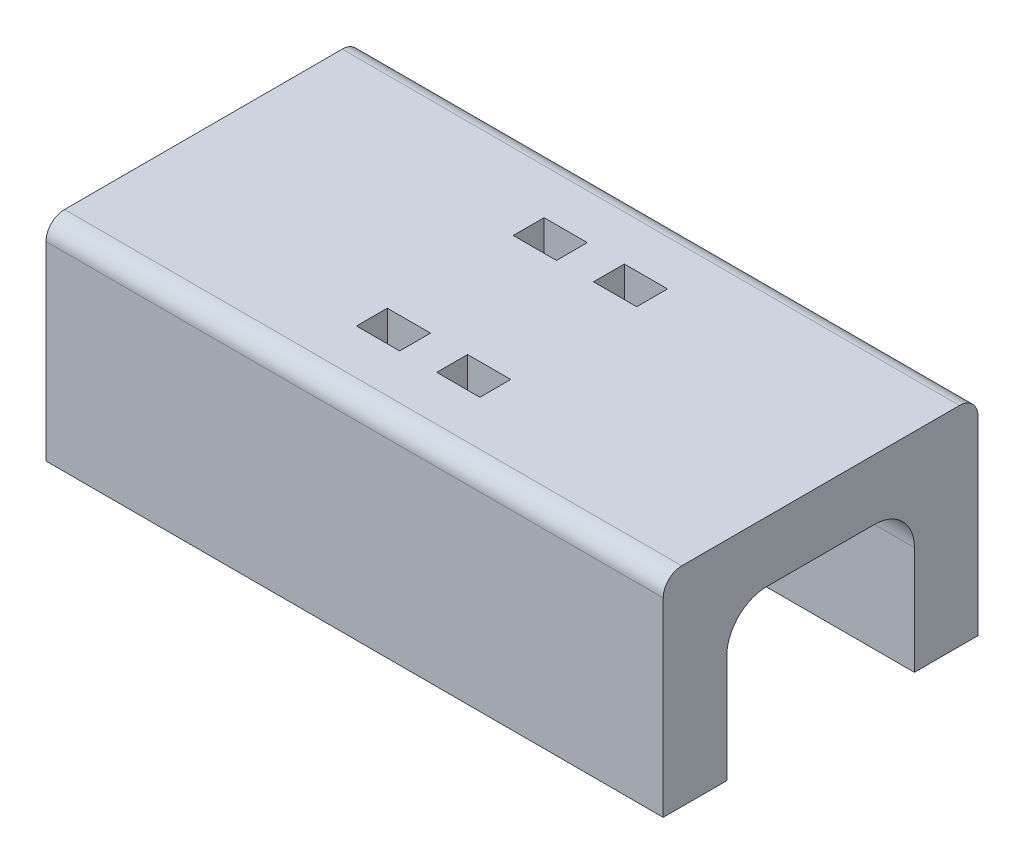
SolidWorks part; units mm, degrees
ref_plane "Front Plane" through (0, 0, 0) normal (0, 0, 1) x (1, 0, 0)
ref_plane "Top Plane" through (0, 0, 0) normal (0, 1, 0) x (1, 0, 0)
ref_plane "Right Plane" through (0, 0, 0) normal (1, 0, 0) x (0, 0, -1)
sketch "Sketch1" plane through (0, 0, 0) normal (0, 1, 0) x (1, 0, 0)
  line L1 (0, 0) -> (50, 0)
  line L2 (0, 0) -> (0, 25.5)
  line L3 (0, 25.5) -> (50, 25.5)
  line L4 (50, 0) -> (50, 25.5)
  dimension "D1" = 50
  dimension "D2" = 25.5
extrude "Boss-Extrude1" add sketch "Sketch1" along normal blind 16.9
sketch "Sketch3" plane through (0, 0, 0) normal (0, -1, 0) x (1, 0, 0)
  line L0 (50, 0) -> (50, -25.5) construction
  line L1 (0, -20.35) -> (50, -20.35)
  line L2 (0, -20.35) -> (0, -5.15)
  line L3 (0, -5.15) -> (50, -5.15)
  line L4 (50, -20.35) -> (50, -5.15)
  line L5 (0, -20.35) -> (50, -5.15) construction
  line L6 (0, -5.15) -> (50, -20.35) construction
  line L7 (0, 0) -> (50, 0) construction
  point P0 (25, -12.75)
  point P7 (25, 0)
  dimension "D1" = 50
  dimension "D2" = 15.2
  dimension "D3" = 12.75
extrude "Cut-Extrude1" cut sketch "Sketch3" against normal blind 12
sketch "Sketch4" plane through (0, 12, 0) normal (0, -1, 0) x (1, 0, 0)
  line L6 (50, -5.15) -> (0, -5.15) construction
  line L7 (20, -20.5) -> (30, -20.5)
  line L8 (20, -20.5) -> (20, -5.15)
  line L9 (20, -5.15) -> (30, -5.15)
  line L10 (30, -20.5) -> (30, -5.15)
  point P12 (25, -12.75)
  dimension "D1" = 10
extrude "Boss-Extrude2" add sketch "Sketch4" along normal blind 12
sketch "Sketch5" plane through (0, 0, 0) normal (0, -1, 0) x (1, 0, 0)
  line L1 (20, -5.15) -> (23.5, -5.15)
  line L2 (20, -5.15) -> (20, -7.65)
  line L3 (20, -7.65) -> (23.5, -7.65)
  line L4 (23.5, -5.15) -> (23.5, -7.65)
  line L5 (30, -5.15) -> (26.5, -5.15)
  line L6 (30, -5.15) -> (30, -7.65)
  line L7 (30, -7.65) -> (26.5, -7.65)
  line L8 (26.5, -5.15) -> (26.5, -7.65)
  line L9 (30, -20.35) -> (26.5, -20.35)
  line L10 (30, -20.35) -> (30, -17.85)
  line L11 (30, -17.85) -> (26.5, -17.85)
  line L12 (26.5, -20.35) -> (26.5, -17.85)
  line L13 (20, -20.35) -> (23.5, -20.35)
  line L14 (20, -20.35) -> (20, -17.85)
  line L15 (20, -17.85) -> (23.5, -17.85)
  line L16 (23.5, -20.35) -> (23.5, -17.85)
  dimension "D1" = 3.5
  dimension "D2" = 2.5
  dimension "D3" = 2.5
  dimension "D4" = 3.5
  dimension "D5" = 3.5
  dimension "D6" = 2.5
  dimension "D7" = 2.5
  dimension "D8" = 3.5
extrude "Cut-Extrude2" cut sketch "Sketch5" against normal through all
sketch "Sketch6" plane through (30, 0, 0) normal (1, 0, 0) x (0, 0, -1)
  circle A0 centre (12.75, 6) radius 2.5
  dimension "D1" = 5
extrude "Cut-Extrude3" cut sketch "Sketch6" against normal blind 2
sketch "Sketch7" plane through (20, 0, 0) normal (-1, 0, 0) x (0, 0, 1)
  circle A0 centre (-12.75, 6) radius 2.5
  dimension "D1" = 5
extrude "Cut-Extrude4" cut sketch "Sketch7" against normal blind 2
sketch "Sketch8" plane through (0, 0, 0) normal (0, -1, 0) x (1, 0, 0)
  line L0 (0, -2.575) -> (50, -2.575) construction
  line L10 (0, -5.15) -> (0, 0) construction
  line L12 (50, 0) -> (50, -5.15) construction
  line L13 (0, -22.925) -> (50, -22.925) construction
  line L14 (0, -25.5) -> (0, -20.35) construction
  line L15 (50, -20.35) -> (50, -25.5) construction
  line L16 (30, -17.85) -> (30, -7.65) construction
  line L17 (0, 0) -> (50, 0) construction
  circle A0 centre (25, -12.75) radius 1.15
  circle A1 centre (6.25, -2.575) radius 1.15
  circle A2 centre (43.75, -2.575) radius 1.15
  circle A3 centre (6.25, -22.925) radius 1.15
  circle A4 centre (43.75, -22.925) radius 1.15
  point P23 (30, -12.75)
  point P26 (25, 0)
  dimension "D1" = 2.3
  dimension "D2" = 2.3
  dimension "D3" = 2.3
  dimension "D4" = 2.3
  dimension "D5" = 2.3
  dimension "D6" = 6.25
  dimension "D7" = 6.25
  dimension "D8" = 6.25
  dimension "D9" = 6.25
  dimension "D10" = 5
  dimension "D11" = 12.75
extrude "Cut-Extrude5" cut sketch "Sketch8" against normal blind 5
fillet "Fillet2" radius 0.35 2 edges at (30, 6, -15.25) (20, 6, -10.25)
fillet "Fillet3" radius 3.25 4 edges at (10, 12, -20.35) (40, 12, -20.35) (40, 12, -5.15) (10, 12, -5.15)
fillet "Fillet4" radius 1 4 edges at (30, 5.9561, -17.85) (30, 5.9561, -7.65) (20, 5.9561, -7.65) (20, 5.9561, -17.85)
fillet "Fillet5" radius 1.5 2 edges at (25, 16.9, 0) (25, 16.9, -25.5)
